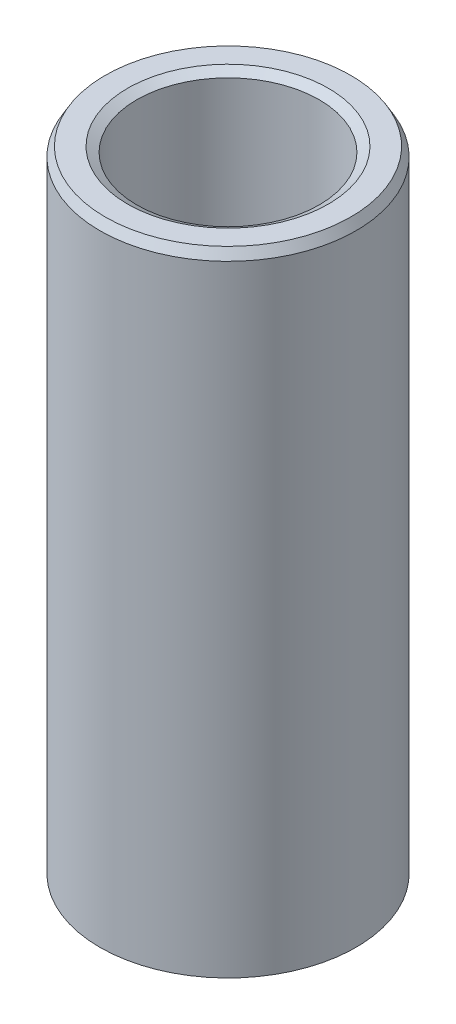
SolidWorks part; units mm, degrees
ref_plane "Front Plane" through (0, 0, 0) normal (0, 0, 1) x (1, 0, 0)
ref_plane "Top Plane" through (0, 0, 0) normal (0, 1, 0) x (1, 0, 0)
ref_plane "Right Plane" through (0, 0, 0) normal (1, 0, 0) x (0, 0, -1)
sketch "Sketch1" plane through (0, 0, 0) normal (0, 1, 0) x (1, 0, 0)
  circle A0 centre (0, 0) radius 15
  dimension "SLEEVE_OD" = 30
extrude "Boss-Extrude1" add sketch "Sketch1" along normal blind 74.3858
sketch "Sketch2" plane through (0, 0, 0) normal (0, 1, 0) x (1, 0, 0)
  circle A0 centre (0, 0) radius 10.6804
  dimension "BORE_D" = 21.3608
extrude "Cut-Extrude1" cut sketch "Sketch2" along normal through all
chamfer "Chamfer1" distance 1.0783 angle 30 4 edges at (0, 74.3858, 10.6804) (0, 0, 10.6804) (0, 0, 15) (0, 74.3858, 15) first distance on face at (0, 74.3858, 10.6804) first distance on face at (0, 0, 10.6804) first distance on face at (0, 74.3858, 15)
